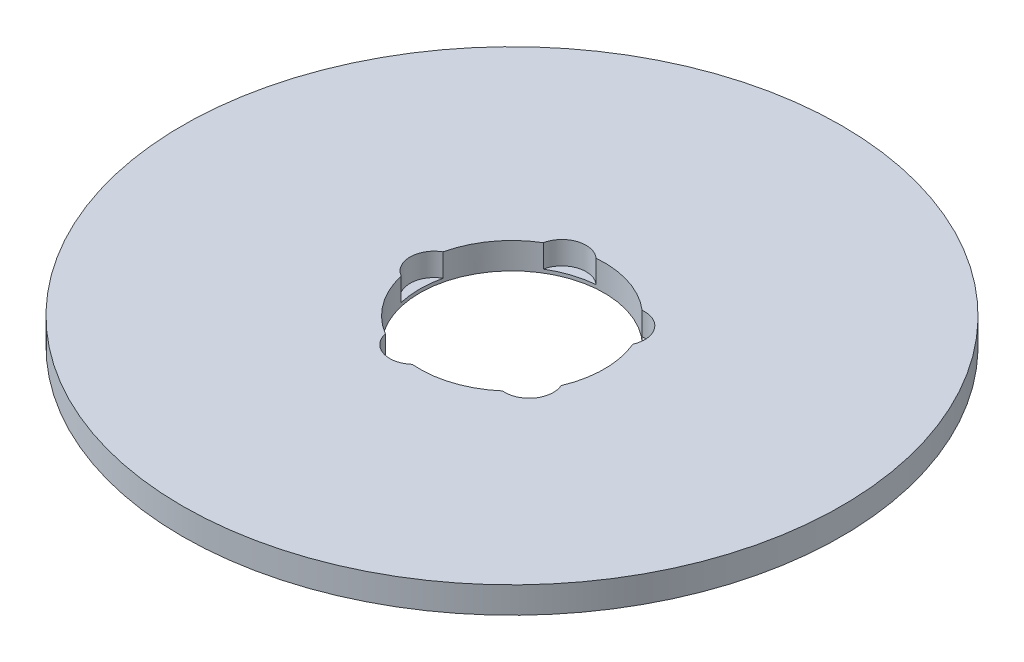
SolidWorks part; units mm, degrees
ref_plane "Front Plane" through (0, 0, 0) normal (0, 0, 1) x (1, 0, 0)
ref_plane "Top Plane" through (0, 0, 0) normal (0, 1, 0) x (1, 0, 0)
ref_plane "Right Plane" through (0, 0, 0) normal (1, 0, 0) x (0, 0, -1)
sketch "Sketch1" plane through (0, 0, 0) normal (0, 1, 0) x (1, 0, 0)
  circle A0 centre (0, 0) radius 62.5
  dimension "FLANGE_OD" = 125
extrude "Boss-Extrude1" add sketch "Sketch1" along normal blind 5
sketch "Sketch2" plane through (0, 0, 0) normal (0, 1, 0) x (1, 0, 0)
  circle A0 centre (0, 0) radius 17.5
  dimension "BORE_D" = 35
extrude "Cut-Extrude1" cut sketch "Sketch2" along normal through all
sketch "Sketch3" plane through (0, 5, 0) normal (0, 1, 0) x (1, 0, 0)
  circle A0 centre (0, 0) radius 14.7497 construction
  circle A1 centre (-14.7497, 0) radius 4.5857
  dimension "BOLT_D" = 9.1713
  dimension "BOLT_PCD" = 29.4993
extrude "Cut-Extrude2" cut sketch "Sketch3" against normal blind 4.3439
pattern_circular "CirPattern1" count 5 over 360 about axis through (0, 0, 0) along (0, 1, 0) of "Cut-Extrude2"
